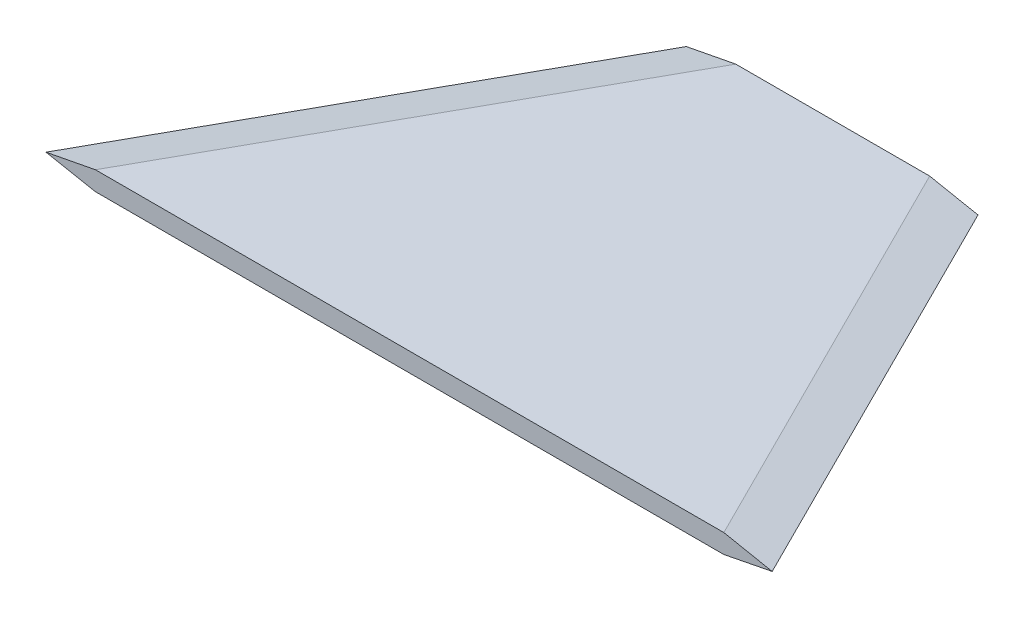
SolidWorks part; units mm, degrees
material "Thornel Mat VMA"
ref_plane "Front Plane" through (0, 0, 0) normal (0, 0, 1) x (1, 0, 0)
ref_plane "Top Plane" through (0, 0, 0) normal (0, 1, 0) x (1, 0, 0)
ref_plane "Right Plane" through (0, 0, 0) normal (1, 0, 0) x (0, 0, -1)
sketch "Sketch1" plane through (0, 0, 0) normal (0, 1, 0) x (1, 0, 0)
  line L0 (0, 0) -> (203.2, 0)
  line L1 (203.2, 0) -> (146.05, 114.3)
  line L2 (146.05, 114.3) -> (63.5, 114.3)
  line L3 (63.5, 114.3) -> (0, 0)
  point P4 (0, 0)
  point P5 (0, 0)
  dimension "D1" = 203.2
  dimension "D2" = 82.55
  dimension "D3" = 114.3
  dimension "D4" = 63.5
extrude "Fin Cut" add sketch "Sketch1" along normal blind 5.2832
chamfer "Chamfer1" distance 2.794 distance2 12.7 1 edges at (174.625, 5.2832, -57.15) first distance on face at (174.625, 2.6416, -57.15)
chamfer "Chamfer2" distance 12.7 distance2 2.794 1 edges at (174.625, 0, -57.15) first distance on face at (103.1875, 0, -57.15)
chamfer "Chamfer3" distance 2.794 distance2 12.7 1 edges at (31.75, 5.2832, -57.15) first distance on face at (31.75, 2.6416, -57.15)
chamfer "Chamfer4" distance 12.7 distance2 2.794 1 edges at (31.75, 0, -57.15) first distance on face at (96.088, 0, -57.15)
